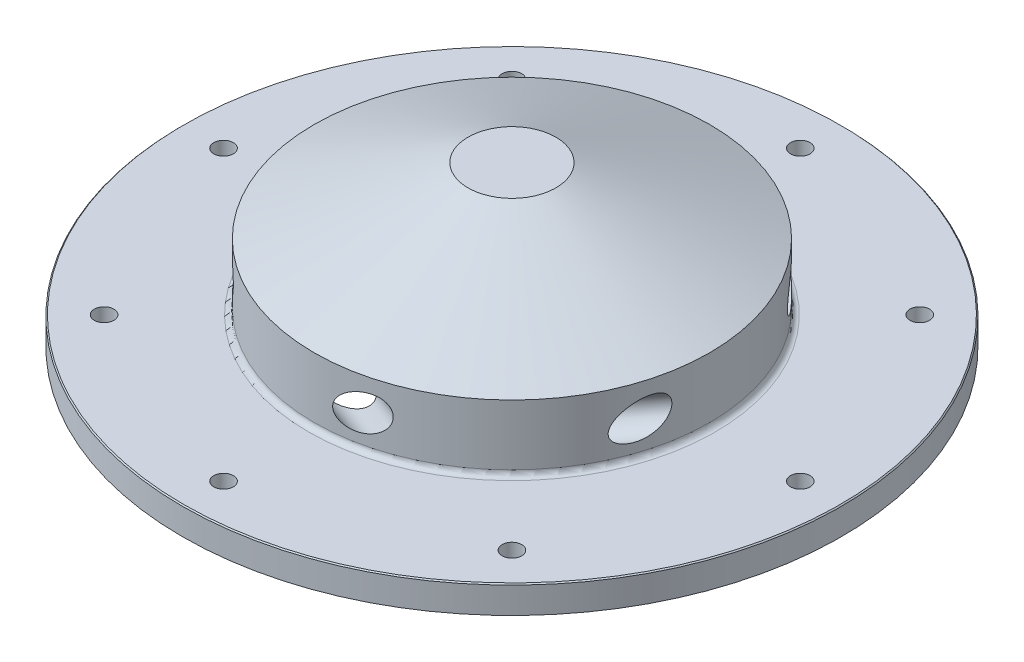
SolidWorks part; units mm, degrees
material "7075-T6 (SN)"
ref_plane "Front Plane" through (0, 0, 0) normal (0, 0, 1) x (1, 0, 0)
ref_plane "Top Plane" through (0, 0, 0) normal (0, 1, 0) x (1, 0, 0)
ref_plane "Right Plane" through (0, 0, 0) normal (1, 0, 0) x (0, 0, -1)
sketch "Sketch2" plane through (0, 0, 0) normal (0, 1, 0) x (1, 0, 0)
  circle A0 centre (0, 0) radius 38.1
  dimension "D1" = 76.2
extrude "Boss-Extrude1" add sketch "Sketch2" along normal blind 3.175
hole_wizard "Tap Drill for #4-40 Tap1" positions "Sketch3" profile "Sketch4" hole size "#4-40" standard "ANSI Inch" end condition through all
sketch "Sketch3" plane through (0, 0, 0) normal (0, -1, 0) x (-1, 0, 0)
  point P0 (0, -33.3375)
  dimension "D1" = 33.3375
sketch "Sketch4" plane through (0, 0, 33.3375) normal (1, 0, 0) x (0, 0, -1)
  line L0 (0, 0) -> (0, 3.175)
  line L1 (0, 3.175) -> (1.1303, 3.175)
  line L2 (1.1303, 3.175) -> (1.1303, 0)
  line L5 (1.1303, 0) -> (0, 0)
  line L11 (0, -6.35) -> (0, 107.95) construction
  dimension "Thru Hole Dia." = 2.2606
  dimension "Thru Hole Depth" = 3.175
pattern_circular "CirPattern1" count 8 over 360 about axis through (0, 0, 0) along (0, 1, 0) of "Tap Drill for #4-40 Tap1"
sketch "Sketch5" plane through (0, 3.175, 0) normal (0, 1, 0) x (1, 0, 0)
  circle A0 centre (0, 0) radius 28.575
  dimension "D1" = 57.15
sketch "Sketch7" plane through (0, 3.175, 0) normal (0, 1, 0) x (1, 0, 0)
  circle A0 centre (0, 0) radius 22.86
  dimension "D1" = 45.72
extrude "Boss-Extrude2" add sketch "Sketch7" along normal blind 7.62
sketch "Sketch8" plane through (0, 0, 0) normal (0, -1, 0) x (1, 0, 0)
  circle A0 centre (0, 0) radius 19.05
  dimension "D1" = 38.1
extrude "Cut-Extrude1" cut sketch "Sketch8" against normal blind 8.89
sketch "Sketch13" plane through (0, 10.795, 0) normal (0, 1, 0) x (1, 0, 0)
  circle A0 centre (0, 0) radius 22.86
  circle A1 centre (0, 0) radius 22.86 construction
  dimension "D1" = 0
ref_plane "Plane2" through (0, 18.415, 0) normal (0, 1, 0) x (1, 0, 0)
sketch "Sketch14" plane through (0, 18.415, 0) normal (0, 1, 0) x (1, 0, 0)
  circle A0 centre (0, 0) radius 5.08
  dimension "D1" = 10.16
loft "Loft2" add profiles "Sketch14", "Sketch13" connector at (-0.0647, 18.415, 5.0796) connector at (0, 10.795, 22.86)
fillet "Fillet1" radius 0.635 1 edges at (0, 8.89, -19.05)
chamfer "Chamfer1" distance 0.127 angle 45 1 edges at (0, 3.175, 38.1)
ref_plane "Plane4" through (0, 7.62, 0) normal (0, 1, 0) x (1, 0, 0)
fillet "Fillet2" radius 0.635 1 edges at (0, 3.175, 22.86)
ref_axis "Axis1" through (41.91, 7.62, 0) along (-1, 0, 0)
ref_plane "Plane3" through (0, 0.5104, 1.905) normal (0, 0.2588, 0.9659) x (-1, 0, 0)
sketch "Sketch16" plane through (0, 0.5104, 1.905) normal (0, 0.2588, 0.9659) x (-1, 0, 0)
  circle A0 centre (16.712, -2.7899) radius 1.9844
  dimension "D1" = 3.9688
  dimension "D2" = 16.712
  dimension "D3" = 2.7899
extrude "Cut-Extrude2" cut sketch "Sketch16" along normal through all
pattern_circular "CirPattern2" count 6 over 360 about axis through (0, 10.795, 0) along (0, 1, 0) of "Cut-Extrude2"
